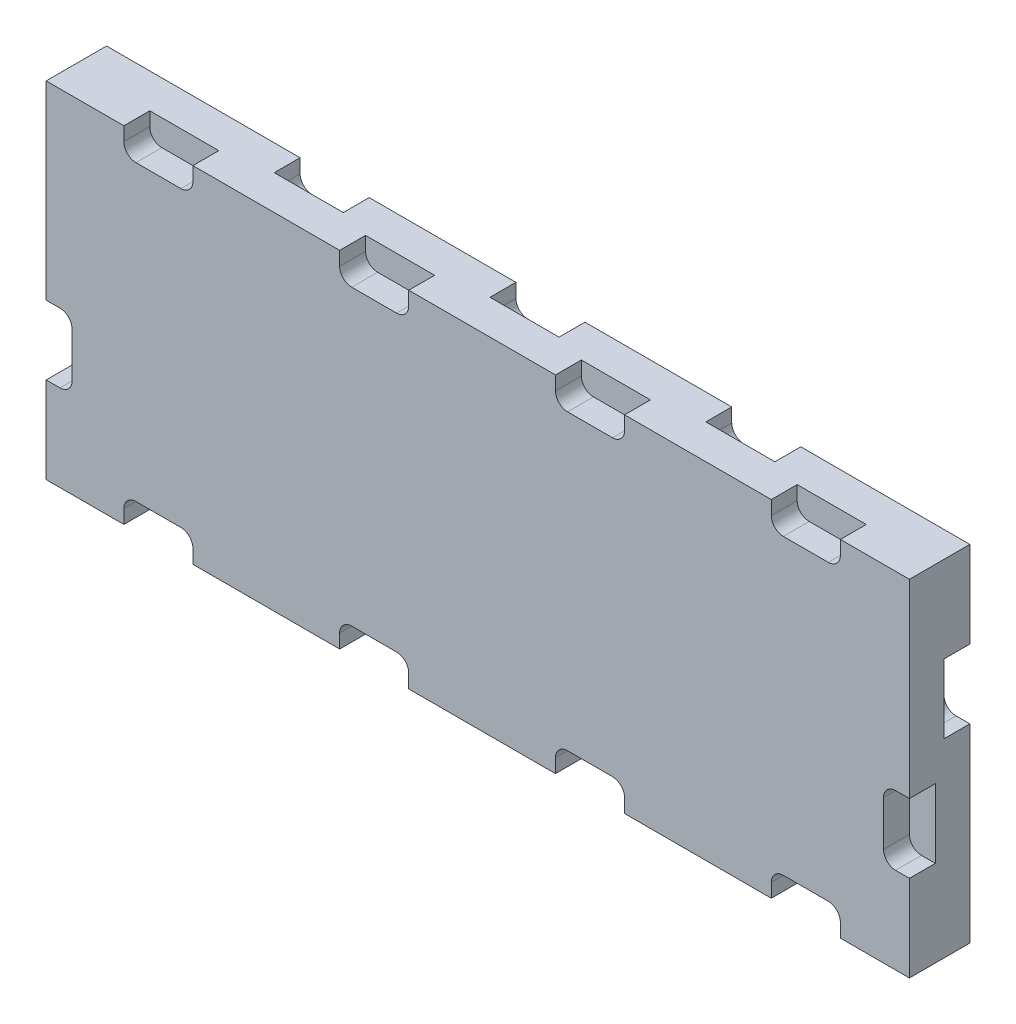
SolidWorks part; units mm, degrees
material "POM Acetal Copolymer"
ref_plane "Front Plane" through (0, 0, 0) normal (0, 0, 1) x (1, 0, 0)
ref_plane "Top Plane" through (0, 0, 0) normal (0, 1, 0) x (1, 0, 0)
ref_plane "Right Plane" through (0, 0, 0) normal (1, 0, 0) x (0, 0, -1)
sketch "Sketch1" plane through (0, 0, 0) normal (0, 0, 1) x (1, 0, 0)
  line L1 (-250, 100) -> (250, 100)
  line L2 (-250, 100) -> (-250, -100)
  line L3 (-250, -100) -> (250, -100)
  line L4 (250, 100) -> (250, -100)
  line L5 (-250, 100) -> (250, -100) construction
  line L6 (-250, -100) -> (250, 100) construction
  point P0 (0, 0)
  dimension "D1" = 500
  dimension "D2" = 200
extrude "Boss-Extrude1" add sketch "Sketch1" along normal blind 35
sketch "Sketch2" plane through (0, 0, 35) normal (0, 0, 1) x (1, 0, 0)
  line L0 (-250, -100) -> (250, -100) construction
  line L1 (-205, -100) -> (-165, -100)
  line L2 (-205, -100) -> (-205, -92)
  line L3 (-198, -85) -> (-172, -85)
  line L4 (-165, -100) -> (-165, -92)
  line L5 (-250, 100) -> (-250, -100) construction
  line L6 (-250, 0) -> (250, 0) construction
  line L7 (250, -100) -> (250, 100) construction
  line L9 (-198, 85) -> (-172, 85)
  line L10 (-165, 100) -> (-165, 92)
  line L11 (-205, 100) -> (-165, 100)
  line L12 (-205, 100) -> (-205, 92)
  line L13 (-80, -100) -> (-80, -92)
  line L14 (-80, -100) -> (-40, -100)
  line L15 (-40, -100) -> (-40, -92)
  line L16 (-73, -85) -> (-47, -85)
  line L17 (-73, 85) -> (-47, 85)
  line L18 (-40, 100) -> (-40, 92)
  line L19 (-80, 100) -> (-40, 100)
  line L20 (-80, 100) -> (-80, 92)
  line L21 (45, -100) -> (45, -92)
  line L22 (45, -100) -> (85, -100)
  line L23 (85, -100) -> (85, -92)
  line L24 (52, -85) -> (78, -85)
  line L25 (52, 85) -> (78, 85)
  line L26 (85, 100) -> (85, 92)
  line L27 (45, 100) -> (85, 100)
  line L28 (45, 100) -> (45, 92)
  line L29 (170, -100) -> (170, -92)
  line L30 (170, -100) -> (210, -100)
  line L31 (210, -100) -> (210, -92)
  line L32 (177, -85) -> (203, -85)
  line L33 (177, 85) -> (203, 85)
  line L34 (210, 100) -> (210, 92)
  line L35 (170, 100) -> (210, 100)
  line L36 (170, 100) -> (170, 92)
  line L37 (0, -100) -> (0, 100) construction
  line L38 (-250, -50) -> (-242, -50)
  line L39 (-250, -50) -> (-250, -10)
  line L40 (-250, -10) -> (-242, -10)
  line L41 (-235, -43) -> (-235, -17)
  line L42 (250, 100) -> (-250, 100) construction
  line L43 (250, -10) -> (242, -10)
  line L44 (235, -43) -> (235, -17)
  line L45 (250, -50) -> (242, -50)
  line L46 (250, -50) -> (250, -10)
  arc A0 (-165, -92) -> (-172, -85) centre (-172, -92) ccw
  arc A1 (-198, -85) -> (-205, -92) centre (-198, -92) ccw
  arc A2 (-165, 92) -> (-172, 85) centre (-172, 92) cw
  arc A3 (-198, 85) -> (-205, 92) centre (-198, 92) cw
  arc A4 (-73, -85) -> (-80, -92) centre (-73, -92) ccw
  arc A5 (-40, -92) -> (-47, -85) centre (-47, -92) ccw
  arc A6 (-40, 92) -> (-47, 85) centre (-47, 92) cw
  arc A7 (-73, 85) -> (-80, 92) centre (-73, 92) cw
  arc A8 (52, -85) -> (45, -92) centre (52, -92) ccw
  arc A9 (85, -92) -> (78, -85) centre (78, -92) ccw
  arc A10 (85, 92) -> (78, 85) centre (78, 92) cw
  arc A11 (52, 85) -> (45, 92) centre (52, 92) cw
  arc A12 (177, -85) -> (170, -92) centre (177, -92) ccw
  arc A13 (210, -92) -> (203, -85) centre (203, -92) ccw
  arc A14 (210, 92) -> (203, 85) centre (203, 92) cw
  arc A15 (177, 85) -> (170, 92) centre (177, 92) cw
  arc A16 (-242, -10) -> (-235, -17) centre (-242, -17) cw
  arc A17 (-235, -43) -> (-242, -50) centre (-242, -43) cw
  arc A18 (242, -10) -> (235, -17) centre (242, -17) ccw
  arc A19 (235, -43) -> (242, -50) centre (242, -43) ccw
  point P10 (-185, -100)
  point P81 (-235, -50)
  dimension "D1" = 7
  dimension "D8" = 7
  dimension "D2" = 15
  dimension "D3" = 40
  dimension "D4" = 45
  dimension "D6" = 125
  dimension "D7" = 15
  dimension "D9" = 50
  dimension "D5" = 4
extrude "Cut-Extrude1" cut sketch "Sketch2" against normal blind 15
sketch "Sketch3" plane through (0, 0, 0) normal (0, 0, -1) x (-1, 0, 0)
  line L0 (250, -100) -> (-250, -100) construction
  line L1 (137.9108, -100) -> (97.9108, -100)
  line L2 (137.9108, -100) -> (137.9108, -92)
  line L3 (130.9108, -85) -> (104.9108, -85)
  line L4 (97.9108, -100) -> (97.9108, -92)
  line L6 (250, 0) -> (-250, 0) construction
  line L7 (250, 100) -> (250, -100) construction
  line L8 (-250, -100) -> (-250, 100) construction
  line L9 (130.9108, 85) -> (104.9108, 85)
  line L10 (97.9108, 100) -> (97.9108, 92)
  line L11 (137.9108, 100) -> (97.9108, 100)
  line L12 (137.9108, 100) -> (137.9108, 92)
  line L13 (12.9108, -100) -> (12.9108, -92)
  line L14 (12.9108, -100) -> (-27.0892, -100)
  line L15 (-27.0892, -100) -> (-27.0892, -92)
  line L16 (5.9108, -85) -> (-20.0892, -85)
  line L17 (5.9108, 85) -> (-20.0892, 85)
  line L18 (-27.0892, 100) -> (-27.0892, 92)
  line L19 (12.9108, 100) -> (-27.0892, 100)
  line L20 (12.9108, 100) -> (12.9108, 92)
  line L21 (-112.0892, -100) -> (-112.0892, -92)
  line L22 (-112.0892, -100) -> (-152.0892, -100)
  line L23 (-152.0892, -100) -> (-152.0892, -92)
  line L24 (-119.0892, -85) -> (-145.0892, -85)
  line L25 (-119.0892, 85) -> (-145.0892, 85)
  line L26 (-152.0892, 100) -> (-152.0892, 92)
  line L27 (-112.0892, 100) -> (-152.0892, 100)
  line L28 (-112.0892, 100) -> (-112.0892, 92)
  line L29 (0, 0) -> (0, -100) construction
  line L30 (-250, 100) -> (250, 100) construction
  line L31 (250, 50) -> (242, 50)
  line L32 (250, 50) -> (250, 10)
  line L33 (250, 10) -> (242, 10)
  line L34 (235, 43) -> (235, 17)
  line L35 (-250, 10) -> (-242, 10)
  line L36 (-235, 43) -> (-235, 17)
  line L37 (-250, 50) -> (-242, 50)
  line L38 (-250, 50) -> (-250, 10)
  arc A0 (97.9108, -92) -> (104.9108, -85) centre (104.9108, -92) cw
  arc A1 (130.9108, -85) -> (137.9108, -92) centre (130.9108, -92) cw
  arc A2 (97.9108, 92) -> (104.9108, 85) centre (104.9108, 92) ccw
  arc A3 (130.9108, 85) -> (137.9108, 92) centre (130.9108, 92) ccw
  arc A4 (5.9108, -85) -> (12.9108, -92) centre (5.9108, -92) cw
  arc A5 (-27.0892, -92) -> (-20.0892, -85) centre (-20.0892, -92) cw
  arc A6 (-27.0892, 92) -> (-20.0892, 85) centre (-20.0892, 92) ccw
  arc A7 (5.9108, 85) -> (12.9108, 92) centre (5.9108, 92) ccw
  arc A8 (-119.0892, -85) -> (-112.0892, -92) centre (-119.0892, -92) cw
  arc A9 (-152.0892, -92) -> (-145.0892, -85) centre (-145.0892, -92) cw
  arc A10 (-152.0892, 92) -> (-145.0892, 85) centre (-145.0892, 92) ccw
  arc A11 (-119.0892, 85) -> (-112.0892, 92) centre (-119.0892, 92) ccw
  arc A12 (242, 10) -> (235, 17) centre (242, 17) cw
  arc A13 (235, 43) -> (242, 50) centre (242, 43) cw
  arc A14 (-242, 10) -> (-235, 17) centre (-242, 17) ccw
  arc A15 (-235, 43) -> (-242, 50) centre (-242, 43) ccw
  point P8 (97.9108, -85)
  point P64 (246, 50)
  point P71 (235, 50)
  dimension "D3" = 7
  dimension "D7" = 7
  dimension "D1" = 15
  dimension "D2" = 40
  dimension "D5" = 50
  dimension "D6" = 15
  dimension "D4" = 3
extrude "Cut-Extrude2" cut sketch "Sketch3" against normal blind 15
equation "\"D7@Sketch2\"=\"D2@Sketch2\""
equation "\"D6@Sketch3\"=\"D1@Sketch3\""
